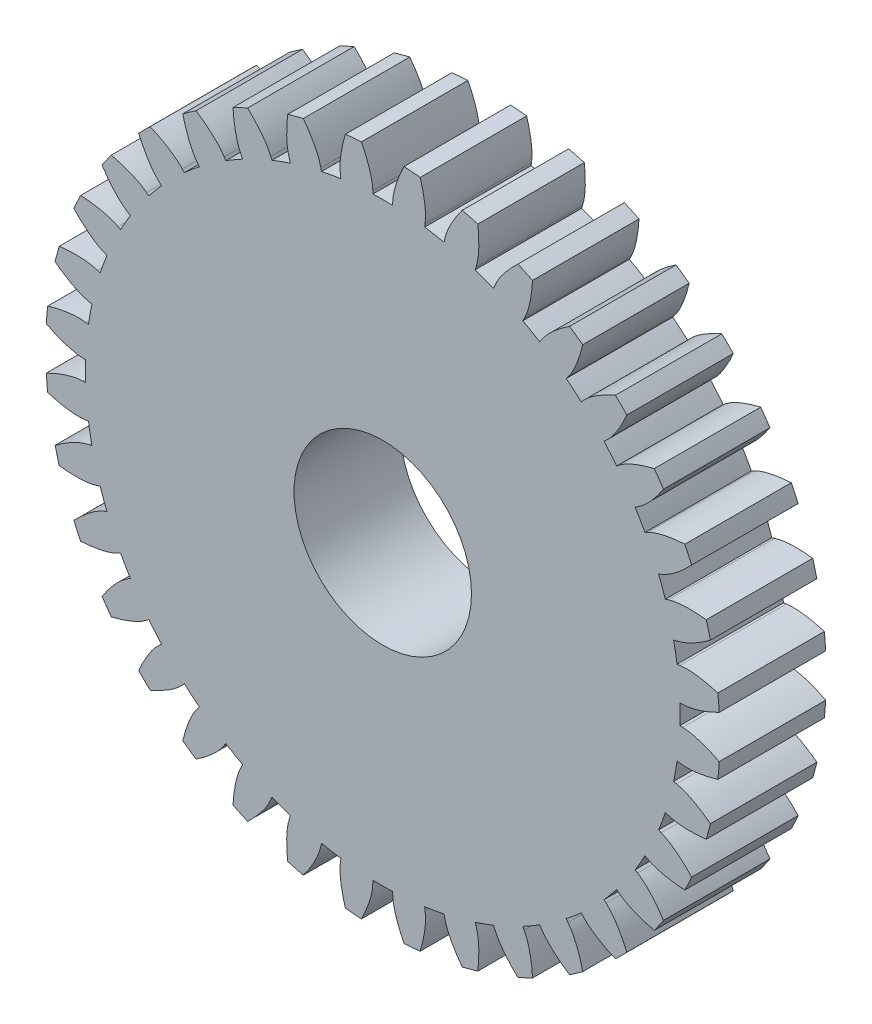
SolidWorks part; units mm, degrees
ref_plane "前视基准面" through (0, 0, 0) normal (0, 0, 1) x (1, 0, 0)
ref_plane "上视基准面" through (0, 0, 0) normal (0, 1, 0) x (1, 0, 0)
ref_plane "右视基准面" through (0, 0, 0) normal (1, 0, 0) x (0, 0, -1)
other "Configuration Table"
sketch "草图1" plane through (0, 0, 0) normal (0, 0, 1) x (1, 0, 0)
  line L0 (0, 0) -> (3.6, 0) construction
  line L1 (0, 0) -> (3.5966, 0.157) construction
  line L2 (0, 0) -> (3.381, 0.112)
  line L3 (3.5966, 0.157) -> (3.5966, -0.157) construction
  line L4 (0, 0) -> (3.381, -0.112)
  circle A0 centre (0, 0) radius 3.8
  circle A1 centre (0, 0) radius 3.6 construction
  circle A2 centre (0, 0) radius 3.35
  circle A3 centre (0, 0) radius 3.3829 construction
  circle A4 centre (0, 0) radius 1
  spline S0 degree 4 poles (3.381, 0.112) (3.4068, 0.1129) (3.4786, 0.1206) (3.6122, 0.1567) (3.8186, 0.2443) (4.0657, 0.3983) (4.3517, 0.6388) (4.641, 0.9681) (4.9035, 1.3715) (5.1787, 1.9586) (5.3541, 2.5843) (5.441, 3.2533) (5.4347, 4.056) (5.3255, 4.8527) (5.0648, 5.7502) (4.6247, 6.6904) (4.0541, 7.5571) (3.3722, 8.3386) (2.5962, 9.0265) (1.743, 9.6151) (0.8269, 10.1008) (-0.0158, 10.434) (-0.7616, 10.6539) (-1.3282, 10.7795) (-1.7135, 10.8471) (-2.0273, 10.8924) (-2.2969, 10.9228) (-2.5087, 10.9435) (-2.7499, 10.9593) (-2.9945, 10.9718) (-3.2391, 10.9781) (-3.6692, 10.9794) (-4.0193, 10.9593) (-4.3829, 10.9359) (-4.5587, 10.9128) (-4.6763, 10.901) knots 0 0 0 0 0 0.005604 0.015718 0.02996 0.048734 0.068727 0.096889 0.125051 0.153212 0.209535 0.237696 0.271429 0.327752 0.384075 0.440398 0.496721 0.553044 0.609367 0.66569 0.722013 0.778336 0.806497 0.834659 0.84874 0.86282 0.876901 0.890982 0.900036 0.909091 0.931818 0.954545 0.977273 1 1 1 1 1 construction
  spline S1 degree 4 poles (3.381, 0.112) (3.4068, 0.1129) (3.4786, 0.1206) (3.6122, 0.1567) (3.8186, 0.2443) (4.0657, 0.3983) (4.3517, 0.6388) (4.641, 0.9681) (4.9035, 1.3715) (5.1787, 1.9586) (5.3541, 2.5843) (5.441, 3.2533) (5.4347, 4.056) (5.3255, 4.8527) (5.0648, 5.7502) (4.6247, 6.6904) (4.0541, 7.5571) (3.3722, 8.3386) (2.5962, 9.0265) (1.743, 9.6151) (0.8269, 10.1008) (-0.0158, 10.434) (-0.7616, 10.6539) (-1.3282, 10.7795) (-1.7135, 10.8471) (-2.0273, 10.8924) (-2.2969, 10.9228) (-2.5087, 10.9435) (-2.7499, 10.9593) (-2.8933, 10.9666) (-2.9691, 10.9697) (-3.0068, 10.971) knots 0 0 0 0 0 0.005604 0.015718 0.02996 0.048734 0.068727 0.096889 0.125051 0.153212 0.209535 0.237696 0.271429 0.327752 0.384075 0.440398 0.496721 0.553044 0.609367 0.66569 0.722013 0.778336 0.806497 0.834659 0.84874 0.86282 0.876901 0.890982 0.900036 0.909091 0.909091 0.909091 0.909091 0.909091
  spline S2 degree 4 poles (3.381, -0.112) (3.4068, -0.1129) (3.4786, -0.1206) (3.6122, -0.1567) (3.8186, -0.2443) (4.0657, -0.3983) (4.3517, -0.6388) (4.641, -0.9681) (4.9035, -1.3715) (5.1787, -1.9586) (5.3541, -2.5843) (5.441, -3.2533) (5.4347, -4.056) (5.3255, -4.8527) (5.0648, -5.7502) (4.6247, -6.6904) (4.0541, -7.5571) (3.3722, -8.3386) (2.5962, -9.0265) (1.743, -9.6151) (0.8269, -10.1008) (-0.0158, -10.434) (-0.7616, -10.6539) (-1.3282, -10.7795) (-1.7135, -10.8471) (-2.0273, -10.8924) (-2.2969, -10.9228) (-2.5087, -10.9435) (-2.7499, -10.9593) (-2.9945, -10.9718) (-3.2391, -10.9781) (-3.6692, -10.9794) (-4.0193, -10.9593) (-4.3829, -10.9359) (-4.5587, -10.9128) (-4.6763, -10.901) knots 0 0 0 0 0 0.005604 0.015718 0.02996 0.048734 0.068727 0.096889 0.125051 0.153212 0.209535 0.237696 0.271429 0.327752 0.384075 0.440398 0.496721 0.553044 0.609367 0.66569 0.722013 0.778336 0.806497 0.834659 0.84874 0.86282 0.876901 0.890982 0.900036 0.909091 0.931818 0.954545 0.977273 1 1 1 1 1 construction
  spline S3 degree 4 poles (3.381, -0.112) (3.4068, -0.1129) (3.4786, -0.1206) (3.6122, -0.1567) (3.8186, -0.2443) (4.0657, -0.3983) (4.3517, -0.6388) (4.641, -0.9681) (4.9035, -1.3715) (5.1787, -1.9586) (5.3541, -2.5843) (5.441, -3.2533) (5.4347, -4.056) (5.3255, -4.8527) (5.0648, -5.7502) (4.6247, -6.6904) (4.0541, -7.5571) (3.3722, -8.3386) (2.5962, -9.0265) (1.743, -9.6151) (0.8269, -10.1008) (-0.0158, -10.434) (-0.7616, -10.6539) (-1.3282, -10.7795) (-1.7135, -10.8471) (-2.0273, -10.8924) (-2.2969, -10.9228) (-2.5087, -10.9435) (-2.7499, -10.9593) (-2.8933, -10.9666) (-2.9691, -10.9697) (-3.0068, -10.971) knots 0 0 0 0 0 0.005604 0.015718 0.02996 0.048734 0.068727 0.096889 0.125051 0.153212 0.209535 0.237696 0.271429 0.327752 0.384075 0.440398 0.496721 0.553044 0.609367 0.66569 0.722013 0.778336 0.806497 0.834659 0.84874 0.86282 0.876901 0.890982 0.900036 0.909091 0.909091 0.909091 0.909091 0.909091
  point P15 (3.5966, 0)
  dimension "齿顶圆直径" = 7.6
  dimension "分度圆直径" = 7.2
  dimension "齿根圆直径" = 6.7
  dimension "基圆直径" = 6.7658
  dimension "内孔直径" = 2
  dimension "渐近线镜像线夹角" = 2.5
extrude "凸台-拉伸1" add sketch "草图1" along normal blind 1.2 contours A0 | A4
extrude "切除-拉伸1" cut sketch "草图1<3>" along normal through all contours A2 S3 A0 S1 region at (3.6055, 0, 0)
sketch "草图1<3>" plane through (0, 0, 0) normal (0, 0, 1) x (1, 0, 0) same geometry as "草图1"
pattern_circular "阵列(圆周)1" count 36 every 10 about axis through (0, 0, 1.2) along (0, 0, 1) of "切除-拉伸1"
equation "\"m\"= 0.2'模数"
equation "\"z\" = 36'齿数"
equation "\"a\"= 20度'压力角"
equation "\"d\"= \"m\" * \"z\"'分度圆直径"
equation "\"da\"= ( \"z\" + 2 ) * \"m\"'齿顶圆直径"
equation "\"df\"= ( \"z\" - 2.5 ) * \"m\"'齿根圆直径"
equation "\"s\"= 0.5 * PI * \"m\"'分度圆齿厚"
equation "\"r\"= 0.38 * \"m\"'齿根圆角"
equation "\"B\"= 0.3 * \"d\"'齿厚"
equation "\"db\"= \"m\" * \"z\" * cos ( \"a\" )'基圆直径"
equation "\"rb\"= \"db\" / 2'基圆半径"
equation "\"齿顶圆直径@草图1\"= \"da\""
equation "\"分度圆直径@草图1\"= \"d\""
equation "\"齿根圆直径@草图1\"= \"df\""
equation "\"基圆直径@草图1\"= \"db\""
equation "\"渐近线镜像线夹角@草图1\"= 360 / 4 / \"z\""
equation "\"h\"= 1.2'齿轮厚度"
equation "\"ir\"= 2'内孔直径"
equation "\"内孔直径@草图1\"= \"ir\""
equation "\"齿轮厚@凸台-拉伸1\"= \"h\""
equation "\"齿轮夹角@阵列(圆周)1\"= 360 / \"z\""
equation "\"齿数@阵列(圆周)1\"= \"z\""
